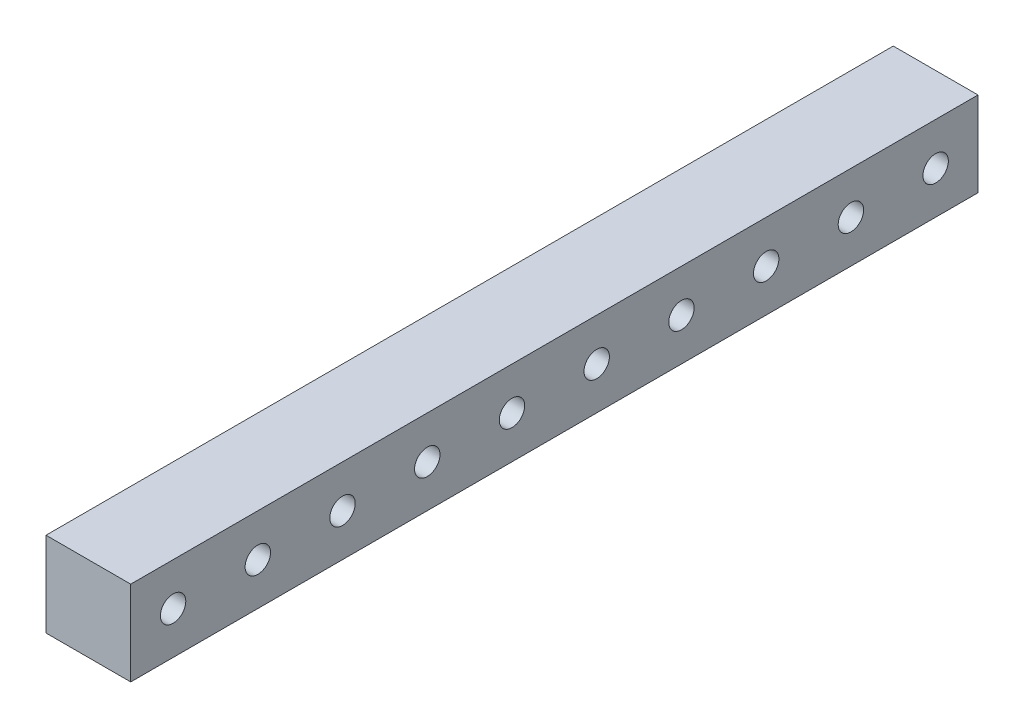
SolidWorks part; units mm, degrees
ref_plane "Front Plane" through (0, 0, 0) normal (0, 0, 1) x (1, 0, 0)
ref_plane "Top Plane" through (0, 0, 0) normal (0, 1, 0) x (1, 0, 0)
ref_plane "Right Plane" through (0, 0, 0) normal (1, 0, 0) x (0, 0, -1)
sketch "Sketch1" plane through (0, 0, 0) normal (0, 0, 1) x (1, 0, 0)
  line L0 (-10, -10) -> (10, 10) construction
  line L1 (-10, 10) -> (10, 10)
  line L2 (-10, 10) -> (-10, -10)
  line L3 (-10, -10) -> (10, -10)
  line L4 (10, 10) -> (10, -10)
  point P4 (0, 0)
  dimension "D1" = 20
  dimension "D2" = 45
extrude "Boss-Extrude1" add sketch "Sketch1" along normal blind 200
hole_wizard "Ø6.0mm Dowel Hole1" positions "Sketch2" profile "Sketch3" hole size "Ø6.0" standard "ANSI Metric" end condition through all
sketch "Sketch2" plane through (10, 0, 0) normal (1, 0, 0) x (0, 0, -1)
  line L0 (0, -10) -> (0, 10) construction
  point P0 (-10, 0)
  point P7 (0, 0)
  dimension "D1" = 10
sketch "Sketch3" plane through (10, 0, 10) normal (0, 1, 0) x (0, 0, -1)
  line L0 (0, 0) -> (0, 20)
  line L1 (0, 20) -> (3, 20)
  line L2 (3, 20) -> (3, 0)
  line L5 (3, 0) -> (0, 0)
  line L11 (0, -6.35) -> (0, 107.95) construction
  dimension "Thru Hole Dia." = 6
  dimension "Thru Hole Depth" = 20
pattern_linear "LPattern2" count 10 spacing 20 along (0, 0, 1) of "Ø6.0mm Dowel Hole1"
